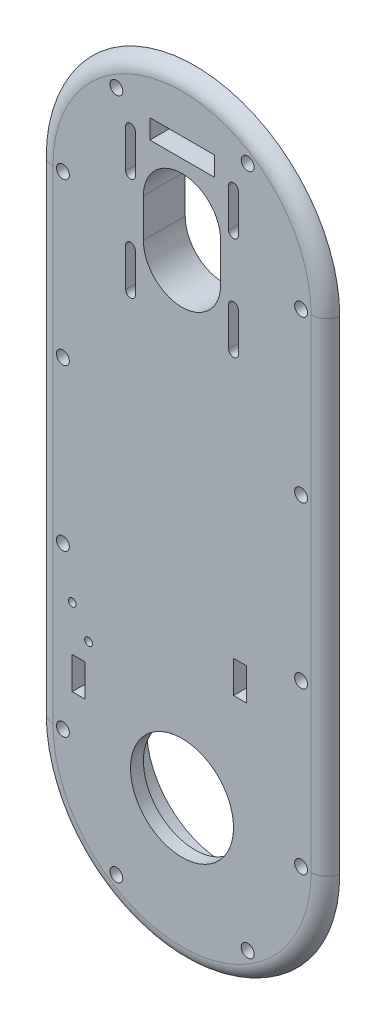
SolidWorks part; units mm, degrees
ref_plane "Plano frontal" through (0, 0, 0) normal (0, 0, 1) x (1, 0, 0)
ref_plane "Plano superior" through (0, 0, 0) normal (0, 1, 0) x (1, 0, 0)
ref_plane "Plano direito" through (0, 0, 0) normal (1, 0, 0) x (0, 0, -1)
sketch "Esboço1" plane through (0, 0, 0) normal (0, 0, 1) x (1, 0, 0)
  line L2 (45, 0) -> (45, 150)
  line L3 (-45, 150) -> (-45, 0)
  line L4 (0, 156) -> (0, 144) construction
  line L9 (0, 0) -> (0, 150) construction
  line L13 (12, 156) -> (12, 144)
  line L16 (-12, 156) -> (-12, 144)
  line L19 (15.99, 159.99) -> (15.99, 171.99) construction
  line L22 (15.99, 134.01) -> (-15.99, 134.01) construction
  line L27 (15.99, 134.01) -> (15.99, 165.99) construction
  line L28 (15.99, 165.99) -> (-15.99, 165.99) construction
  line L29 (-15.99, 134.01) -> (-15.99, 165.99) construction
  line L30 (15.99, 134.01) -> (-15.99, 165.99) construction
  line L31 (15.99, 165.99) -> (-15.99, 134.01) construction
  line L32 (14.49, 159.99) -> (14.49, 171.99)
  line L33 (17.49, 159.99) -> (17.49, 171.99)
  line L34 (-15.99, 159.99) -> (-15.99, 171.99) construction
  line L35 (-17.49, 159.99) -> (-17.49, 171.99)
  line L36 (-14.49, 159.99) -> (-14.49, 171.99)
  line L37 (15.99, 128.01) -> (15.99, 140.01) construction
  line L38 (14.49, 128.01) -> (14.49, 140.01)
  line L39 (17.49, 128.01) -> (17.49, 140.01)
  line L40 (-15.99, 128.01) -> (-15.99, 140.01) construction
  line L41 (-17.49, 128.01) -> (-17.49, 140.01)
  line L42 (-14.49, 128.01) -> (-14.49, 140.01)
  arc A8 (-45, 0) -> (45, 0) centre (0, 0) ccw
  arc A9 (45, 150) -> (-45, 150) centre (0, 150) ccw
  circle A10 centre (0, 0) radius 16
  arc A26 (12, 156) -> (-12, 156) centre (0, 156) ccw
  arc A29 (-12, 144) -> (12, 144) centre (0, 144) ccw
  arc A30 (14.49, 159.99) -> (17.49, 159.99) centre (15.99, 159.99) ccw
  arc A31 (17.49, 171.99) -> (14.49, 171.99) centre (15.99, 171.99) ccw
  arc A32 (-17.49, 159.99) -> (-14.49, 159.99) centre (-15.99, 159.99) ccw
  arc A33 (-14.49, 171.99) -> (-17.49, 171.99) centre (-15.99, 171.99) ccw
  arc A34 (14.49, 128.01) -> (17.49, 128.01) centre (15.99, 128.01) ccw
  arc A35 (17.49, 140.01) -> (14.49, 140.01) centre (15.99, 140.01) ccw
  arc A36 (-17.49, 128.01) -> (-14.49, 128.01) centre (-15.99, 128.01) ccw
  arc A37 (-14.49, 140.01) -> (-17.49, 140.01) centre (-15.99, 140.01) ccw
  point P4 (0, 150)
  point P18 (0, 150)
  point P22 (15.99, 165.99)
  point P31 (-15.99, 165.99)
  point P39 (15.99, 134.01)
  point P46 (-15.99, 134.01)
  point P52 (-15.99, 134.01)
  dimension "D1" = 90
  dimension "D2" = 150
  dimension "D3" = 32
  dimension "D4" = 12
  dimension "D6" = 31.98
  dimension "D7" = 31.98
  dimension "D10" = 2
  dimension "D11" = 150
  dimension "D5" = 12
  dimension "D8" = 1.5
  dimension "D9" = 12
  dimension "D12" = 2
extrude "Ressalto-extrusão1" add sketch "Esboço1" along normal blind 4
sketch "Esboço2" plane through (0, 0, 0) normal (0, 0, 1) x (1, 0, 0)
  circle A0 centre (0, 0) radius 24
  circle A1 centre (0, 0) radius 27
  dimension "D1" = 48
  dimension "D2" = 54
extrude "Ressalto-extrusão2" add sketch "Esboço2" against normal blind 9
sketch "Esboço4" plane through (0, 0, 4) normal (0, 0, 1) x (1, 0, 0)
  line L0 (37, 150) -> (37, 0) construction
  line L1 (-37, 150) -> (-37, 0) construction
  line L2 (-37, 75) -> (37, 75) construction
  line L3 (0, 75) -> (0, 150) construction
  arc A0 (-37, 0) -> (37, 0) centre (0, 0) ccw construction
  arc A1 (37, 150) -> (-37, 150) centre (0, 150) ccw construction
  circle A2 centre (-37, 150) radius 2
  circle A3 centre (-37, 100) radius 2
  circle A4 centre (-37, 50) radius 2
  circle A5 centre (-37, 0) radius 2
  circle A6 centre (-20.3971, 180.87) radius 2
  circle A7 centre (-20.3971, -30.87) radius 2
  circle A8 centre (20.3971, -30.87) radius 2
  circle A9 centre (20.3971, 180.87) radius 2
  circle A10 centre (37, 0) radius 2
  circle A11 centre (37, 50) radius 2
  circle A12 centre (37, 100) radius 2
  circle A13 centre (37, 150) radius 2
  dimension "D1" = 74
  dimension "D2" = 4
  dimension "D4" = 30.87
  dimension "D3" = 4
extrude "Corte-extrusão1" cut sketch "Esboço4" against normal up to surface (4 mm away) up to face at (27, 0, 0)
sketch "Esboço6" plane through (0, 0, 0) normal (0, 0, -1) x (-1, 0, 0)
  line L0 (-12, 150) -> (12, 150) construction
  line L1 (-12, 144) -> (-12, 156) construction
  line L2 (12, 156) -> (12, 144) construction
  line L3 (0, 168) -> (0, 150) construction
  line L4 (0, 150) -> (0, 132) construction
  line L5 (0, 144) -> (0, 156) construction
  line L6 (-12, 144) -> (-12, 156)
  line L7 (12, 144) -> (12, 156)
  line L8 (0, 143) -> (0, 157) construction
  line L9 (-14, 143) -> (-14, 157)
  line L10 (14, 143) -> (14, 157)
  arc A2 (12, 156) -> (-12, 156) centre (0, 156) ccw construction
  arc A3 (-12, 144) -> (12, 144) centre (0, 144) ccw construction
  arc A4 (-12, 144) -> (12, 144) centre (0, 144) ccw
  arc A5 (12, 156) -> (-12, 156) centre (0, 156) ccw
  arc A6 (-14, 143) -> (14, 143) centre (0, 143) ccw
  arc A7 (14, 157) -> (-14, 157) centre (0, 157) ccw
  point P3 (0, 150)
  point P11 (0, 150)
  point P26 (0, 150)
  dimension "D1" = 12
  dimension "D2" = 12
  dimension "D3" = 14
  dimension "D4" = 14
extrude "Ressalto-extrusão3" add sketch "Esboço6" along normal blind 9
sketch "Esboço8" plane through (0, 0, -9) normal (0, 0, -1) x (-1, 0, 0)
  line L0 (0, 129) -> (0, 27)
  arc A0 (-14, 143) -> (14, 143) centre (0, 143) ccw construction
  circle A1 centre (0, 0) radius 27 construction
  circle A2 centre (0, 0) radius 27 construction
rib "Nervura4" sketch "Esboço8" sketch "Esboço8" thickness 5 extrusion direction normal to sketch draft on no parameters "D1"=5
sketch "Esboço9" plane through (0, 0, 0) normal (0, 0, -1) x (-1, 0, 0)
  line L0 (0, 0) -> (45, 46.9042) construction
  line L1 (45, 150) -> (45, 0) construction
  line L2 (0, 0) -> (45, 42.6497) construction
  line L3 (-45, 0) -> (-45, 150) construction
  line L4 (34.1051, 11.516) -> (30.1051, 11.516)
  line L5 (34.1051, 11.516) -> (34.1051, 21.516)
  line L6 (34.1051, 21.516) -> (30.1051, 21.516)
  line L7 (30.1051, 11.516) -> (30.1051, 21.516)
  line L8 (-10.0344, 178) -> (9.9656, 178)
  line L9 (-10.0344, 178) -> (-10.0344, 172)
  line L10 (-10.0344, 172) -> (9.9656, 172)
  line L11 (9.9656, 178) -> (9.9656, 172)
  line L12 (-10.0344, 178) -> (9.9656, 172) construction
  line L13 (-10.0344, 172) -> (9.9656, 178) construction
  line L14 (-16, 35.5482) -> (-20, 35.5482)
  line L15 (-16, 35.5482) -> (-16, 45.5482)
  line L16 (-16, 45.5482) -> (-20, 45.5482)
  line L17 (-20, 35.5482) -> (-20, 45.5482)
  circle A0 centre (29.0323, 27.516) radius 1.2
  circle A1 centre (34.1051, 35.5482) radius 1.2
  point P14 (-0.0344, 175)
  point P15 (32.1051, 21.516)
  point P24 (-18, 35.5482)
  dimension "D3" = 2.4
  dimension "D4" = 9.5
  dimension "D5" = 40
  dimension "D1" = 62
  dimension "D2" = 65
  dimension "D6" = 4
  dimension "D7" = 10
  dimension "D8" = 20
  dimension "6" = 6
  dimension "D9" = 6
  dimension "D10" = 175
  dimension "D11" = 10
  dimension "D12" = 4
  dimension "D13" = 25
extrude "Corte-extrusão2" cut sketch "Esboço9" against normal up to surface (4 mm away) up to face at (0, 150, 4)
chamfer "Chanfro1" distance 6 angle 45 8 edges at (10.7471, 134.0278, 0) (14, 150, 0) (-10.7471, 134.0278, 0) (0, 171, 0) (-14, 150, 0) (2.5, 78.0545, 0) (-2.5, 78.0545, 0) (0, -27, 0)
fillet "Filete1" radius 5 4 edges at (0, 195, 4) (45, 75, 4) (0, -45, 4) (-45, 75, 4)
